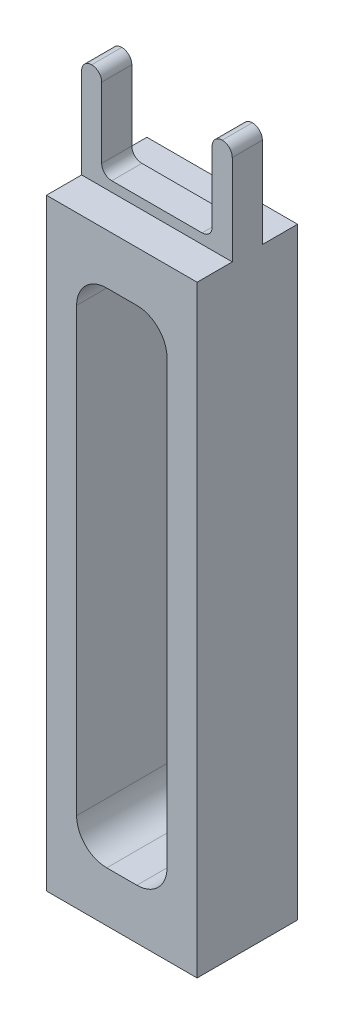
SolidWorks part; units mm, degrees
ref_plane "Front Plane" through (0, 0, 0) normal (0, 0, 1) x (1, 0, 0)
ref_plane "Top Plane" through (0, 0, 0) normal (0, 1, 0) x (1, 0, 0)
ref_plane "Right Plane" through (0, 0, 0) normal (1, 0, 0) x (0, 0, -1)
sketch "Sketch1" plane through (0, 0, 0) normal (0, 1, 0) x (1, 0, 0)
  line L1 (-7.5, -5) -> (7.5, -5)
  line L2 (-7.5, -5) -> (-7.5, 5)
  line L3 (-7.5, 5) -> (7.5, 5)
  line L4 (7.5, -5) -> (7.5, 5)
  line L5 (-7.5, -5) -> (7.5, 5) construction
  line L6 (-7.5, 5) -> (7.5, -5) construction
  point P0 (0, 0)
  dimension "D1" = 10
  dimension "D2" = 15
extrude "Boss-Extrude1" add sketch "Sketch1" along normal blind 60
sketch "Sketch2" plane through (0, 60, 0) normal (0, 1, 0) x (1, 0, 0)
  line L0 (7.5, -5) -> (7.5, 5) construction
  line L1 (-7.5, -1.5) -> (7.5, -1.5)
  line L2 (-7.5, -1.5) -> (-7.5, 1.5)
  line L3 (-7.5, 1.5) -> (7.5, 1.5)
  line L4 (7.5, -1.5) -> (7.5, 1.5)
  line L5 (-7.5, -1.5) -> (7.5, 1.5) construction
  line L6 (-7.5, 1.5) -> (7.5, -1.5) construction
  point P0 (0, 0)
  dimension "D1" = 3
extrude "Boss-Extrude2" add sketch "Sketch2" along normal blind 10
sketch "Sketch3" plane through (0, 0, 1.5) normal (0, 0, 1) x (1, 0, 0)
  line L0 (-7.5, 60) -> (7.5, 60) construction
  line L1 (-5.5, 61) -> (5.5, 61)
  line L2 (-5.5, 61) -> (-5.5, 79.7911)
  line L3 (-5.5, 79.7911) -> (5.5, 79.7911)
  line L4 (5.5, 61) -> (5.5, 79.7911)
  line L5 (-5.5, 61) -> (5.5, 79.7911) construction
  line L6 (-5.5, 79.7911) -> (5.5, 61) construction
  line L7 (7.5, 70) -> (7.5, 60) construction
  line L8 (-7.5, 70) -> (-7.5, 60) construction
  point P0 (0, 70.3955)
  dimension "D1" = 1
  dimension "D2" = 2
  dimension "D3" = 2
extrude "Cut-Extrude1" cut sketch "Sketch3" against normal through all
fillet "Fillet1" radius 1 6 edges at (-5.5, 70, 0) (5.5, 70, 0) (5.5, 61, 0) (-5.5, 61, 0) (-7.5, 70, 0) (7.5, 70, 0)
sketch "Sketch4" plane through (0, 0, 5) normal (0, 0, 1) x (1, 0, 0)
  line L0 (7.5, 60) -> (7.5, 0) construction
  line L1 (-1.5, 5) -> (1.5, 5)
  line L2 (-4.5, 8) -> (-4.5, 52)
  line L3 (-1.5, 55) -> (1.5, 55)
  line L4 (4.5, 8) -> (4.5, 52)
  line L5 (-7.5, 60) -> (-7.5, 0) construction
  line L6 (-7.5, 0) -> (7.5, 0) construction
  arc A0 (-1.5, 5) -> (-4.5, 8) centre (-1.5, 8) cw
  arc A1 (1.5, 5) -> (4.5, 8) centre (1.5, 8) ccw
  arc A2 (1.5, 55) -> (4.5, 52) centre (1.5, 52) cw
  arc A3 (-4.5, 52) -> (-1.5, 55) centre (-1.5, 52) cw
  point P14 (4.5, 5)
  point P17 (4.5, 55)
  dimension "D5" = 3
  dimension "D1" = 50
  dimension "D2" = 3
  dimension "D3" = 3
  dimension "D4" = 5
extrude "Cut-Extrude2" cut sketch "Sketch4" against normal through all
